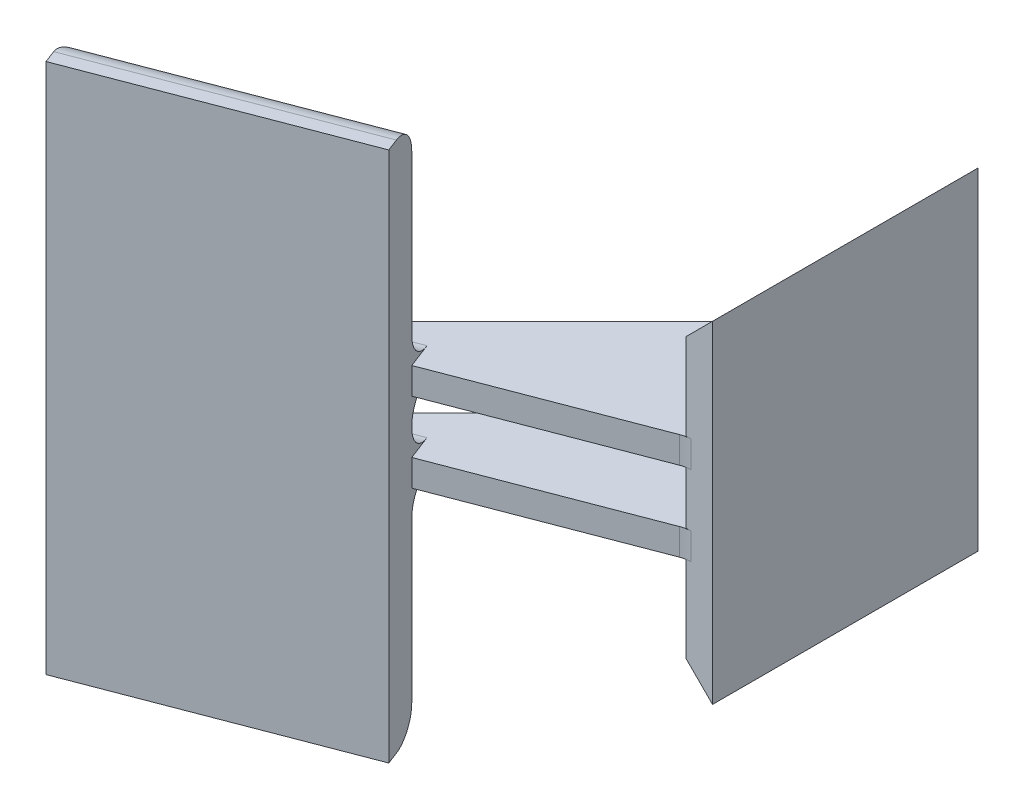
SolidWorks part; units mm, degrees
ref_plane "Front Plane" through (0, 0, 0) normal (1, 0, 0) x (0, 1, 0)
ref_plane "Top Plane" through (0, 0, 0) normal (0, 0, 1) x (0, 1, 0)
ref_plane "Right Plane" through (0, 0, 0) normal (0, 1, 0) x (-1, 0, 0)
sketch "Sketch1" plane through (0, 0, 0) normal (1, 0, 0) x (0, 1, 0)
  line L1 (-12.5, 10) -> (12.5, 10)
  line L2 (-12.5, 10) -> (-12.5, -10)
  line L3 (-12.5, -10) -> (12.5, -10)
  line L4 (12.5, 10) -> (12.5, -10)
  line L5 (-12.5, 10) -> (12.5, -10) construction
  line L6 (-12.5, -10) -> (12.5, 10) construction
  point P0 (0, 0)
  dimension "D1" = 20
  dimension "D2" = 25
extrude "Boss-Extrude1" add sketch "Sketch1" along normal blind 2
sketch "Sketch2" plane through (0, 0, 0) normal (0, 1, 0) x (-1, 0, 0)
  line L0 (0, -5) -> (24.2854, 19.2854)
  line L1 (0, -10) -> (0, 10) construction
  line L3 (-2, -10) -> (0, -10) construction
  line L4 (-2, 10) -> (0, 10) construction
  line L6 (0, 10) -> (0, -5)
  line L7 (0, 10) -> (24.2854, 19.2854)
  dimension "D1" = 45
  dimension "D2" = 5
  dimension "D3" = 0
  dimension "D4" = 26
extrude "Boss-Extrude2" add sketch "Sketch2" along normal mid plane 8
extrude "Cut-Extrude1" cut sketch "Sketch2<2>" against normal mid plane 4
sketch "Sketch2<2>" plane through (0, 0, 0) normal (0, 1, 0) x (-1, 0, 0) same geometry as "Sketch2"
sketch "Sketch5" plane through (3.3358, 0, 8.7246) normal (0.3571, 0, 0.9341) x (0.9341, 0, -0.3571)
  line L1 (-19.5713, -20) -> (-39.5713, -20)
  line L2 (-19.5713, -20) -> (-19.5713, 20)
  line L3 (-19.5713, 20) -> (-39.5713, 20)
  line L4 (-39.5713, -20) -> (-39.5713, 20)
  line L5 (-19.5713, -20) -> (-39.5713, 20) construction
  line L6 (-19.5713, 20) -> (-39.5713, -20) construction
  line L7 (-29.5713, 4) -> (-29.5713, 2) construction
  point P0 (-29.5713, 0)
  point P5 (-31.6526, -0.3935)
  point P6 (0, 0)
  point P8 (0, 0)
  dimension "D1" = 20
  dimension "D2" = 40
extrude "Boss-Extrude5" add sketch "Sketch5" along normal blind 3
fillet "Fillet3" radius 2 9 edges at (-24.2854, -20, 19.2854) (-33.626, 0, 22.8567) (-24.2854, 20, 19.2854) (-19.6151, 4, 17.4998) (-24.2854, 3, 19.2854) (-19.6151, 2, 17.4998) (-19.6151, -4, 17.4998) (-24.2854, -3, 19.2854) (-19.6151, -2, 17.4998)
chamfer "Chamfer1" distance 2 angle 45 3 edges at (0, -12.5, 0) (0, 0, -10) (0, 12.5, 0)
fillet "Fillet4" radius 2 2 edges at (0, 3, 10) (0, -3, 10)
